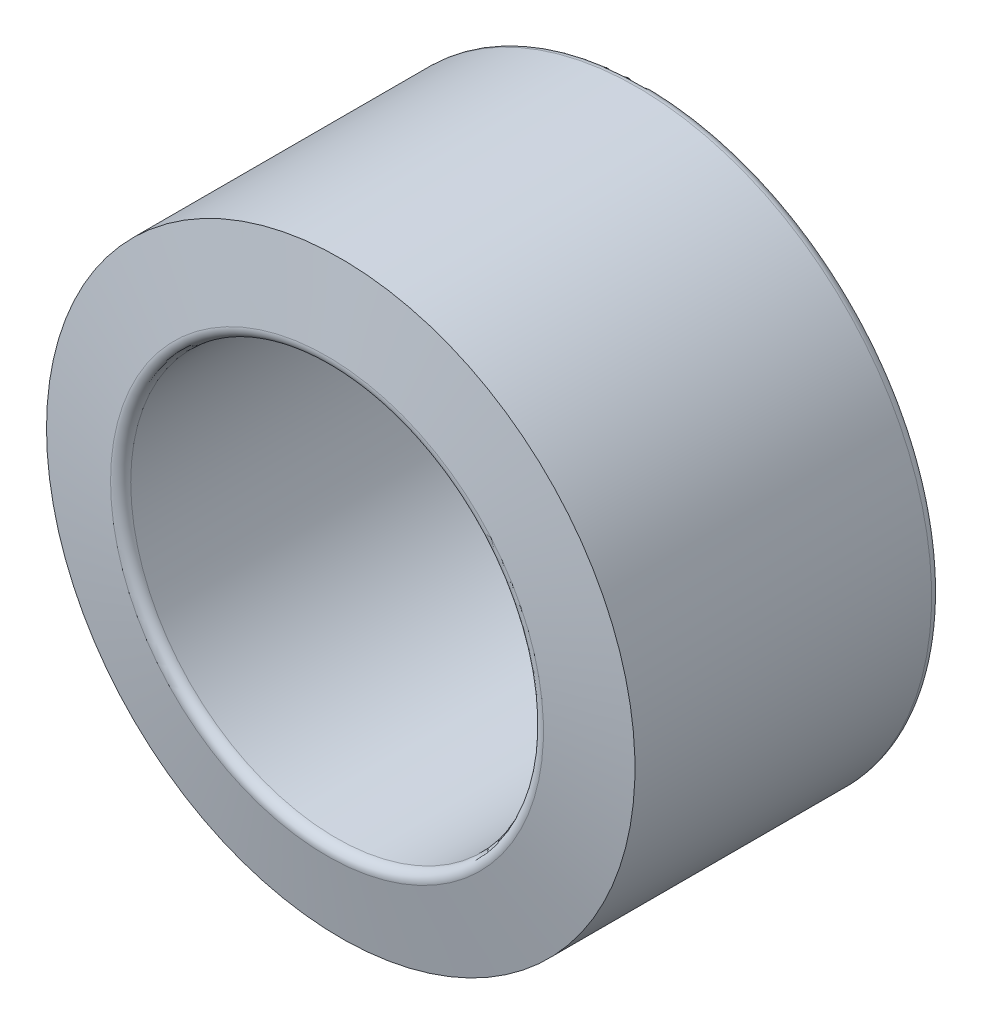
SolidWorks part; units mm, degrees
ref_plane "Front" through (0, 0, 0) normal (0, 0, 1) x (1, 0, 0)
ref_plane "Top" through (0, 0, 0) normal (0, 1, 0) x (1, 0, 0)
ref_plane "Right" through (0, 0, 0) normal (1, 0, 0) x (0, 0, -1)
sketch "Esquisse1" plane through (0, 0, 0) normal (0, 0, 1) x (1, 0, 0)
  circle A0 centre (0, 0) radius 31.5
  circle A1 centre (0, 0) radius 22
  dimension "D1" = 63
  dimension "D2" = 44
extrude "Boss.-Extru.1" add sketch "Esquisse1" along normal blind 36.6
chamfer "Chanfrein1" distance 2 angle 80 2 edges at (31.5, 0, 0) (31.5, 0, 36.6) first distance on face at (31.5, 0, 36.6)
fillet "Congé1" radius 1 3 edges at (31.5, 0, 2) (-22, 0, 36.2751) (22, 0, 0.3249)
